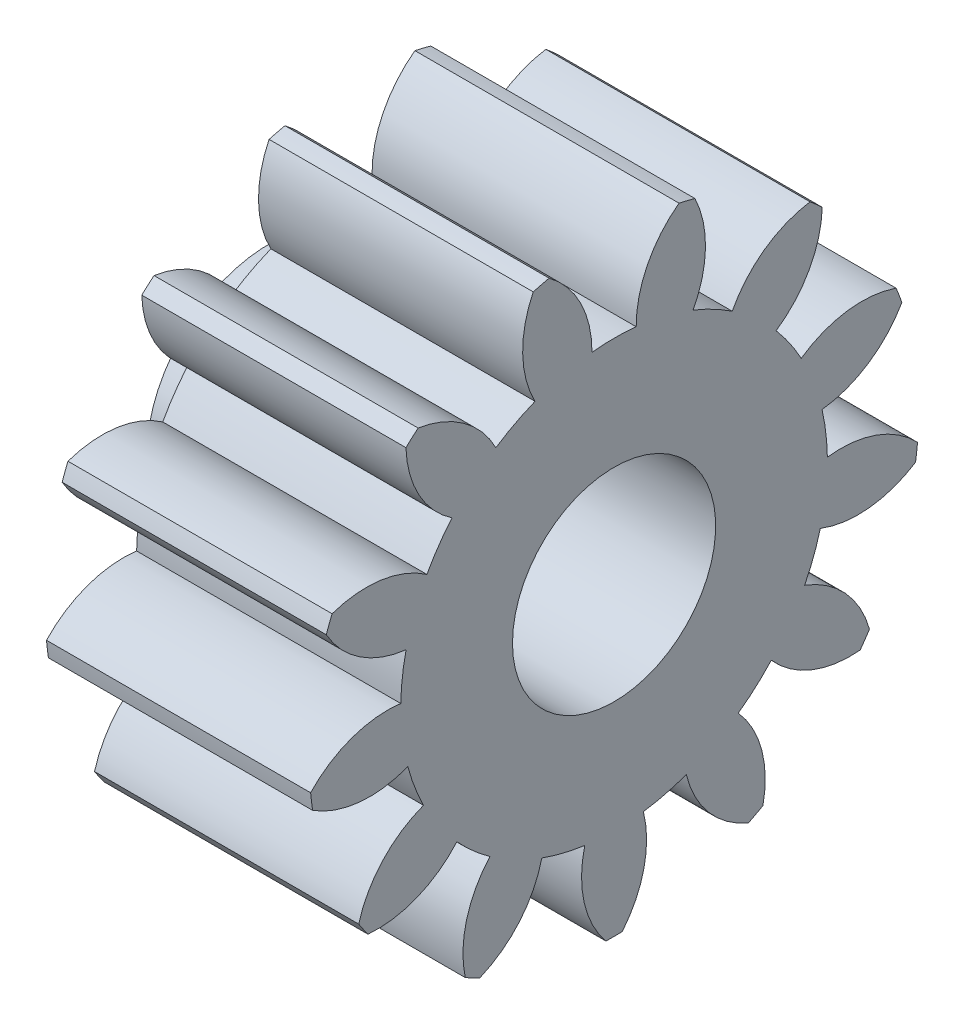
SolidWorks part; units mm, degrees
ref_plane "Plane1" through (0, 0, 0) normal (0, 0, 1) x (1, 0, 0)
ref_plane "Plane2" through (0, 0, 0) normal (0, 1, 0) x (1, 0, 0)
ref_plane "Plane3" through (0, 0, 0) normal (1, 0, 0) x (0, 0, -1)
other "Configuration Table"
sketch "HoldingSke" plane through (0, 0, 0) normal (0, 1, 0) x (1, 0, 0)
  line L0 (0, 0) -> (0.4872, -0.1125)
  line L1 (-15, 0) -> (100, 0) construction
  line L2 (0, 0) -> (-2.1039, 2.3779)
  line L3 (0, 0) -> (-11.863, 4.5341)
  line L4 (0, 0) -> (8.4147, 1.9427)
  line L5 (0, 0) -> (-15.9282, -5.9407)
  line L6 (0, 0) -> (-10.7765, -7.2709)
  line L7 (-2.1039, 2.3779) -> (1.5554, 18.9794)
  line L8 (-76.2, 54.61) -> (-74.4, 54.61)
  line L9 (-71.009, 38.7566) -> (-53.1078, 45.2721)
  line L10 (-76.2, 71.12) -> (104.1128, 71.12)
  line L11 (0, 0) -> (-13, 0)
  line L12 (-76.2, 101.6) -> (-76.133, 101.6)
  line L13 (24.9733, 27.94) -> (52.9518, 28.4284)
  line L14 (24.9733, 27.94) -> (24.9743, 27.94)
  line L15 (24.9733, 27.94) -> (100.4006, 29.5858)
  line L16 (-63.627, -2) -> (-12.827, -2)
  circle A0 centre (0, 0) radius 5
  circle A1 centre (0, 0) radius 6
  circle A2 centre (0, 0) radius 6
  circle A3 centre (0, 0) radius 5
  dimension "Num_teeth" = 13
  dimension "Pitch_radius" = 180.3128
  dimension "Width" = 13
  dimension "Thickness" = 13
sketch "BasProSke" plane through (0, 0, 0) normal (0, 1, 0) x (1, 0, 0)
  line L0 (-10, 0) -> (60, 0) construction
  line L1 (0, 0) -> (0, 15)
  line L2 (0, 0) -> (13, 0)
  line L3 (13, 0) -> (13, 15)
  line L4 (13, 15) -> (0, 15)
  dimension "Thickness" = 13
  dimension "Diameter" = 30
revolve "Base-Revolve" add sketch "BasProSke" angle 360 about L0
sketch "TooCutSke" plane through (0, 0, 0) normal (1, 0, 0) x (0, 0, -1)
  line L1 (0, 0) -> (0, 107) construction
  line L2 (0, 0) -> (-1.6841, 12.8905) construction
  line L3 (0, 0) -> (-6.1834, 25.087) construction
  line L4 (-1.6841, 12.8905) -> (-3.0917, 12.5435) construction
  arc A0 (1.0882, 10.4424) -> (-1.0882, 10.4424) centre (0, 0) ccw
  arc A1 (3.2249, 14.6752) -> (-3.2249, 14.6752) centre (0, 0) ccw
  circle A2 centre (0, 0) radius 13 construction
  circle A3 centre (0, 0) radius 12.216 construction
  arc A4 (-1.0882, 10.4424) -> (-3.2249, 14.6752) centre (-6.2882, 10.4733) ccw
  arc A5 (3.2249, 14.6752) -> (1.0882, 10.4424) centre (6.2882, 10.4733) ccw
extrude "ToothCut" cut sketch "TooCutSke" along normal through all
fillet "Breaks" [suppressed] radius 0.04 tangent propagation no
fillet "RootFillets" [suppressed] radius 0.501
pattern_circular "TeethCuts" count 13 every 27.692 about axis through (-10, 0, 0) along (1, 0, 0) of "ToothCut", "RootFillets", "Breaks"
sketch "HubNeaOneSke" plane through (0, 0, 0) normal (-1, 0, 0) x (0, 0, 1)
  circle A0 centre (0, 0) radius 6
  dimension "Diameter" = 12
extrude "HubNearOne" add sketch "HubNeaOneSke" along normal blind 4.0001
sketch "HubNeaBotSke" plane through (0, 0, 0) normal (-1, 0, 0) x (0, 0, 1)
  circle A0 centre (0, 0) radius 6
  dimension "Diameter" = 12
extrude "HubNearBoth" [suppressed] add sketch "HubNeaBotSke" along normal blind 2
ref_plane "FarPln" through (13, 0, 0) normal (1, 0, 0) x (0, 0, -1)
sketch "HubFarSke" plane through (13, 0, 0) normal (1, 0, 0) x (0, 0, -1)
  circle A0 centre (0, 0) radius 6
  dimension "Diameter" = 12
extrude "HubFar" [suppressed] add sketch "HubFarSke" along normal blind 2
sketch "BorSke" plane through (0, 0, 0) normal (1, 0, 0) x (0, 0, -1)
  circle A0 centre (0, 0) radius 5
  dimension "Diameter" = 10
extrude "Bore" cut sketch "BorSke" along normal mid plane 34.0001
sketch "KeySke" plane through (0, 0, 0) normal (1, 0, 0) x (0, 0, -1)
  line L0 (-2, 0) -> (-2, 6.8)
  line L1 (-2, 6.8) -> (2, 6.8)
  line L2 (2, 6.8) -> (2, 0)
  line L3 (0, 0) -> (0, 34) construction
  line L4 (-2, 0) -> (2, 0)
  dimension "Width" = 4
extrude "Keyway" [suppressed] cut sketch "KeySke" along normal mid plane 34.0001
pattern_circular "Keyway2" [suppressed] count 2 every 90 about axis through (-10, 0, 0) along (1, 0, 0) reverse direction yes
scale "Scale1" scale about centroid uniform scaling yes scale factor 0.317565
equation "' \"Module@HoldingSke\" = 6.35"
equation "' \"Num_teeth@HoldingSke\" = 12"
equation "' \"Ap@HoldingSke\" =  20"
equation "' \"Ap@HoldingSke\" = 20"
equation "' \"Width@HoldingSke\" = 0.5 * 25.4"
equation "' \"Hub_dia@HoldingSke\"= 1 * 25.4"
equation "' \"Hub_dia@HoldingSke\" = 1 * 25.4"
equation "' \"Overall_len@HoldingSke\" = 1.0 * 25.4"
equation "' \"Bore@HoldingSke\" = 0.75 * 25.4"
equation "' \"T_dim@HoldingSke\" = 0.1 * 25.4"
equation "' \"Width@KeySke\" = 0.25 * 25.4"
equation "' \"Show_teeth@HoldingSke\" = 13"
equation "' \"Backlash@HoldingSke\" = 0.009 * 25.4"
equation "' \"Addendum_fac@HoldingSke\" = 1.0"
equation "' \"Dedendum_fac@HoldingSke\" = 1.25"
equation "' \"Dedendum_add@HoldingSke\" = 0.00005 * 25.4"
equation "' \"Clearance_fac@HoldingSke\" = 0.25"
equation "\"Pitch@HoldingSke\" = 1 / \"Module@HoldingSke\""
equation "\"Overcut_dia@TooCutSke\" = (\"Num_teeth@HoldingSke\" + 2 * \"Addendum_fac@HoldingSke\") / \"Pitch@HoldingSke\" + 0.002 * 25.4"
equation "\"Pitch_dia@TooCutSke\" = \"Num_teeth@HoldingSke\" / \"Pitch@HoldingSke\""
equation "\"Base_dia@TooCutSke\" = \"Num_teeth@HoldingSke\" / \"Pitch@HoldingSke\" * cos((\"Ap@HoldingSke\"  * 3.14159265 / 180))"
equation "\"Root_dia@TooCutSke\" = (\"Num_teeth@HoldingSke\" + 2) / \"Pitch@HoldingSke\" - 2 * (\"Addendum_fac@HoldingSke\" + \"Dedendum_fac@HoldingSke\") / \"Pitch@HoldingSke\" - \"Dedendum_add@HoldingSke\" * 2"
equation "\"Half_ang@TooCutSke\" = 180 / \"Num_teeth@HoldingSke\""
equation "\"Half_CT@TooCutSke\" = \"Num_teeth@HoldingSke\" / \"Pitch@HoldingSke\" * sin((3.14159265 / 2 / \"Num_teeth@HoldingSke\")) / 2 - 7 * \"Backlash@HoldingSke\" / 4"
equation "\"Flank_rad@TooCutSke\" = \"Num_teeth@HoldingSke\" / \"Pitch@HoldingSke\" / 5"
equation "\"Radius@RootFillets\" = \"Clearance_fac@HoldingSke\" / \"Pitch@HoldingSke\" + \"Dedendum_add@HoldingSke\""
equation "\"Break_rad@Breaks\" = 0.02 / \"Pitch@HoldingSke\""
equation "\"Thickness@HoldingSke\" = \"Width@HoldingSke\""
equation "\"OAL@HoldingSke\" = \"Thickness@HoldingSke\""
equation "\"MHD@HoldingSke\" = (\"Num_teeth@HoldingSke\" + 2) / \"Pitch@HoldingSke\" - 2 * (\"Addendum_fac@HoldingSke\" + \"Dedendum_fac@HoldingSke\")  / \"Pitch@HoldingSke\" - \"Dedendum_add@HoldingSke\" * 2"
equation "\"MBD@HoldingSke\" = (\"Num_teeth@HoldingSke\" + 2) / \"Pitch@HoldingSke\" - 2 * (\"Addendum_fac@HoldingSke\" + \"Dedendum_fac@HoldingSke\")  / \"Pitch@HoldingSke\" - \"Dedendum_add@HoldingSke\" * 2 - 0.002 * 25.4"
equation "\"MHD@HoldingSke\" = ((sgn( \"MHD@HoldingSke\" - \"Hub_dia@HoldingSke\" )-1)*( \"MHD@HoldingSke\" - \"Hub_dia@HoldingSke\" ))/-2+ \"Hub_dia@HoldingSke\""
equation "\"MBD@HoldingSke\" = ((sgn( \"MBD@HoldingSke\" - \"Bore@HoldingSke\" )-1)*( \"MBD@HoldingSke\" - \"Bore@HoldingSke\" ))/-2+ \"Bore@HoldingSke\""
equation "\"OAL@HoldingSke\" = ((sgn( \"OAL@HoldingSke\" - \"Overall_len@HoldingSke\" )+1)*( \"OAL@HoldingSke\" - \"Overall_len@HoldingSke\" ))/2 + \"Overall_len@HoldingSke\" + 0.000002 * 25.4"
equation "\"Num_teeth@TeethCuts\" = int( \"Show_teeth@HoldingSke\" ) + 1"
equation "\"Num_teeth@TeethCuts\" = ((sgn( \"Num_teeth@TeethCuts\" - \"Num_teeth@HoldingSke\" )-1)*( \"Num_teeth@TeethCuts\" - \"Num_teeth@HoldingSke\" ))/-2+ \"Num_teeth@HoldingSke\""
equation "\"Num_teeth@TeethCuts\" = ((sgn( \"Num_teeth@TeethCuts\" - 2.0)+1)*( \"Num_teeth@TeethCuts\" - 2.0))/2 +2.0"
equation "\"Angle@TeethCuts\" = 360.0 / \"Num_teeth@HoldingSke\""
equation "\"Diameter@BasProSke\" = (\"Num_teeth@HoldingSke\" + 2 * \"Addendum_fac@HoldingSke\") / \"Pitch@HoldingSke\""
equation "\"Thickness@BasProSke\"  = \"Thickness@HoldingSke\""
equation "' \"Fillet_rad@BasProSke\" =  \"Thickness@HoldingSke\" * 0.05"
equation "' \"Fillet_rad@BasProSke\" = \"Thickness@HoldingSke\" * 0.05"
equation "\"MHD@HoldingSke\" = ((sgn( \"MHD@HoldingSke\" - \"Root_dia@TooCutSke\" )-1)*( \"MHD@HoldingSke\" - \"Root_dia@TooCutSke\" ))/-2+ \"Root_dia@TooCutSke\""
equation "\"Diameter@HubNeaOneSke\" = \"MHD@HoldingSke\""
equation "\"Length@HubNearOne\" = \"OAL@HoldingSke\" - \"Thickness@BasProSke\""
equation "\"Diameter@HubNeaBotSke\" = \"MHD@HoldingSke\""
equation "\"Length@HubNearBoth\" = ( \"OAL@HoldingSke\" - \"Thickness@BasProSke\" ) / 2.0"
equation "\"Thickness@FarPln\" = \"Thickness@BasProSke\""
equation "\"Diameter@HubFarSke\" = \"MHD@HoldingSke\""
equation "\"Length@HubFar\" = ( \"OAL@HoldingSke\" - \"Thickness@BasProSke\" ) / 2.0"
equation "\"Diameter@BorSke\" = \"MBD@HoldingSke\""
equation "\"D1@Bore\" = \"OAL@HoldingSke\" * 2.0"
equation "\"D1@Keyway\" = \"OAL@HoldingSke\" * 2.0"
equation "\"Offset@KeySke\" = \"T_dim@HoldingSke\" + \"MBD@HoldingSke\" / 2.0"
